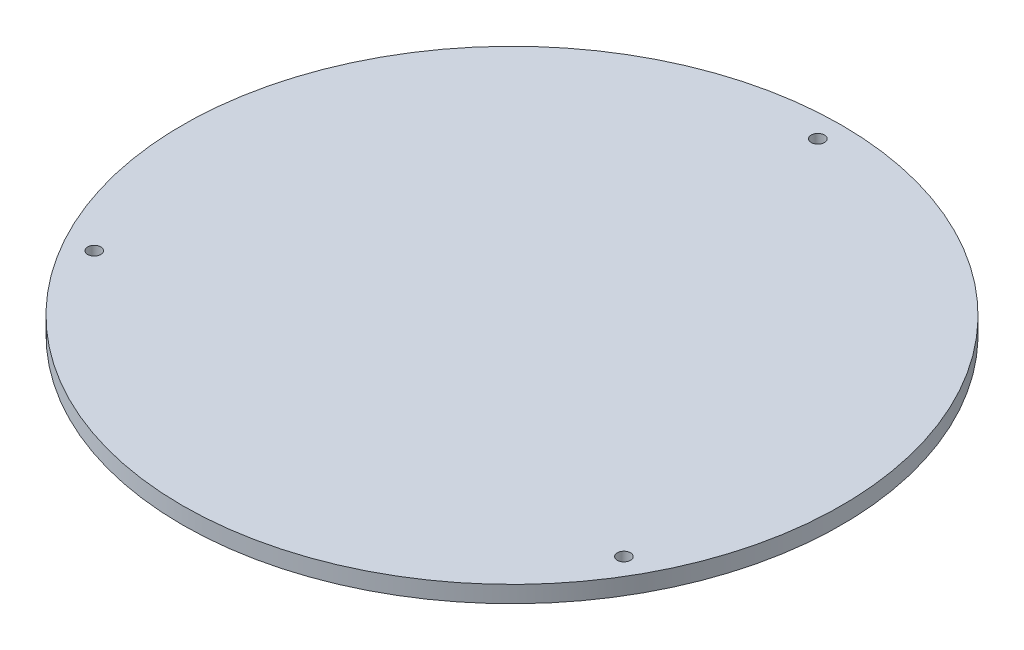
SolidWorks part; units mm, degrees
ref_plane "Front Plane" through (0, 0, 0) normal (0, 0, 1) x (1, 0, 0)
ref_plane "Top Plane" through (0, 0, 0) normal (0, 1, 0) x (1, 0, 0)
ref_plane "Right Plane" through (0, 0, 0) normal (1, 0, 0) x (0, 0, -1)
sketch "Sketch1" plane through (0, 0, 0) normal (0, 1, 0) x (1, 0, 0)
  circle A0 centre (0, 0) radius 125
  circle A1 centre (0, 116) radius 2.5
  dimension "D1" = 250
  dimension "D2" = 5
  dimension "D3" = 9
extrude "Boss-Extrude1" add sketch "Sketch1" along normal blind 6.35 contours A0
sketch "Sketch2" plane through (0, 6.35, 0) normal (0, 1, 0) x (1, 0, 0)
  line L0 (0, 0) -> (0, 125) construction
  line L1 (0, 0) -> (108.2532, -62.5) construction
  line L2 (0, 0) -> (-108.2532, -62.5) construction
  line L3 (0, 0) -> (0, 125) construction
  line L4 (0, 0) -> (108.2532, -62.5) construction
  circle A0 centre (0, 0) radius 125 construction
  circle A1 centre (0, 116) radius 2.5
  circle A2 centre (100.4589, -58) radius 2.5
  circle A3 centre (-100.4589, -58) radius 2.5
  dimension "D3" = 5
  dimension "D2" = 120
  dimension "D4" = 9
  dimension "D1" = 3
ref_plane "Plane1" through (0, 13.35, 0) normal (0, 1, 0) x (1, 0, 0)
sketch "Sketch3" plane through (0, 13.35, 0) normal (0, 1, 0) x (1, 0, 0)
  circle A0 centre (100.4589, -58) radius 2.5 construction
  circle A1 centre (0, 116) radius 2.5 construction
  circle A2 centre (-100.4589, -58) radius 2.5 construction
  point P0 (0, 116)
  point P1 (100.4589, -58)
  point P3 (-100.4589, -58)
extrude "Cut-Extrude1" cut sketch "Sketch2" against normal through all
sketch "Sketch4" plane through (0, 0, 0) normal (0, -1, 0) x (1, 0, 0)
  line L4 (0, -5) -> (0, 5)
  line L12 (-15, 0) -> (15, 0) construction
  line L13 (-35, 10) -> (-15, 10) construction
  line L14 (-15, 20) -> (-20, 20) construction
  line L15 (-25, 0) -> (-20, 0)
  line L16 (-20, 20) -> (-25, 20)
  line L17 (-15, 20) -> (-15, -20)
  line L18 (35, -20) -> (15, -20) construction
  line L19 (5, 0) -> (-5, 0)
  line L20 (15, 20) -> (15, -20)
  line L21 (25, 5) -> (15, 20)
  line L22 (35, 20) -> (25, 5)
  line L23 (35, -20) -> (35, 20)
  arc A1 (-25, 20) -> (-25, 0) centre (-25, 10) ccw
  point P21 (0, 0)
  dimension "D1" = 10
  dimension "D3" = 30
extrude "Cut-Extrude-Thin1" cut sketch "Sketch4" against normal blind 1 thin thin type mid plane wall 1
